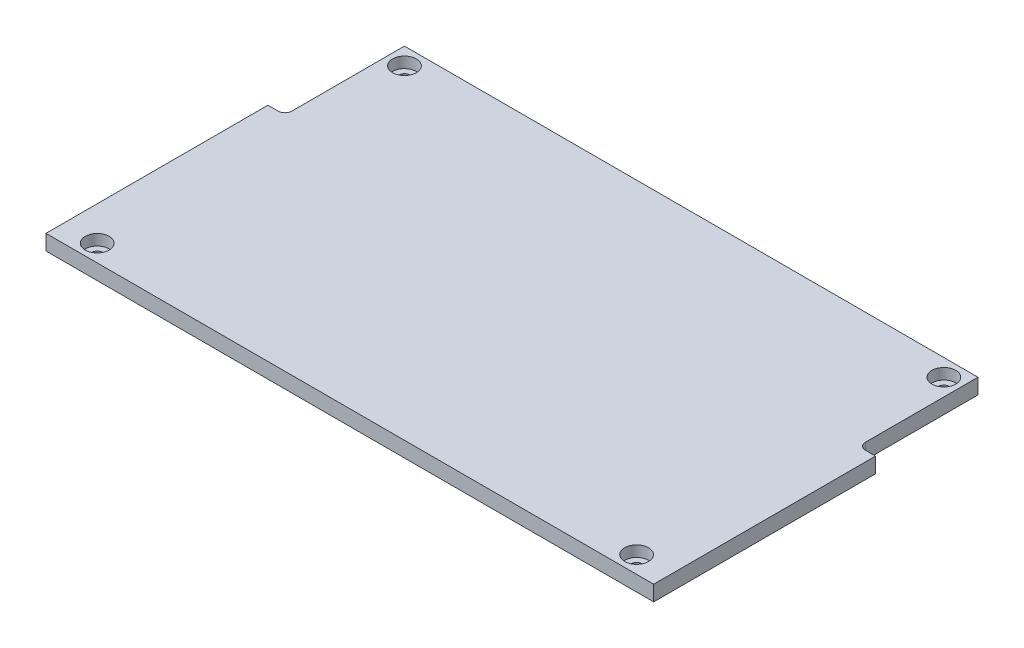
SolidWorks part; units mm, degrees
ref_plane "Ebene vorne" through (0, 0, 0) normal (0, 0, 1) x (1, 0, 0)
ref_plane "Ebene oben" through (0, 0, 0) normal (0, 1, 0) x (1, 0, 0)
ref_plane "Ebene rechts" through (0, 0, 0) normal (1, 0, 0) x (0, 0, -1)
sketch "Skizze1" plane through (0, 0, 0) normal (0, 1, 0) x (1, 0, 0)
  line L1 (0, 0) -> (-89, 0)
  line L2 (0, 0) -> (0, 50)
  line L3 (0, 50) -> (-89, 50)
  line L4 (-89, 0) -> (-89, 50)
  dimension "D1" = 89
  dimension "D2" = 50
extrude "Aufsatz-Linear austragen1" add sketch "Skizze1" along normal blind 4.5
sketch "Skizze3" plane through (0, 4.5, 0) normal (0, 1, 0) x (1, 0, 0)
  line L1 (0, 0) -> (0, 50) construction
  line L2 (-19, 3) -> (-3, 3)
  line L3 (-19, 3) -> (-19, 15)
  line L4 (-19, 15) -> (-3, 15)
  line L5 (-3, 3) -> (-3, 15)
  line L6 (-19, 3) -> (-3, 15) construction
  line L7 (-19, 15) -> (-3, 3) construction
  line L8 (-89, 0) -> (0, 0) construction
  point P0 (-11, 9)
  dimension "D1" = 3
  dimension "D3" = 12
  dimension "D2" = 3
  dimension "D4" = 16
extrude "Schnitt-Linear austragen2" cut sketch "Skizze3" against normal through all
fillet "Verrundung1" radius 2 4 edges at (-19, 2.25, -3) (-3, 2.25, -3) (-3, 2.25, -15) (-19, 2.25, -15)
pattern_linear "Lineares Muster1" count 3 spacing 16 along (0, 0, -1) count 4 spacing 20 along (-1, 0, 0) of "Schnitt-Linear austragen2", "Verrundung1"
sketch "Skizze2" plane through (0, 4.5, 0) normal (0, 1, 0) x (1, 0, 0)
  line L0 (0, 0) -> (0, 50) construction
  line L1 (-89, 0) -> (0, 0) construction
  circle A0 centre (-79, 45) radius 5
  dimension "D1" = 10
  dimension "D2" = 79
  dimension "D3" = 45
extrude "Aufsatz-Linear austragen2" add sketch "Skizze2" against normal up to surface (4.5 mm away) up to face at (-11, 0, -25)
hole_wizard "Stirnsenkung für M3 Flachkopfschraube mit Schlitz1" positions "Skizze4" profile "Skizze5" counterbore size "M3" standard "DIN" end condition through all
sketch "Skizze4" plane through (0, 4.5, 0) normal (0, 1, 0) x (1, 0, 0)
  line L0 (0, 50) -> (-89, 50) construction
  point P0 (-79, 45)
  dimension "D1" = 10
  dimension "D2" = 5
sketch "Skizze5" plane through (-79, 4.5, -45) normal (1, 0, 0) x (0, 0, 1)
  line L0 (0, 0) -> (0, 4.5)
  line L1 (0, 4.5) -> (1.7, 4.5)
  line L3 (1.7, 4.5) -> (1.7, 3.2)
  line L4 (1.7, 3.2) -> (3.5, 3.2)
  line L5 (3.5, 3.2) -> (3.5, 0)
  line L7 (3.5, 0) -> (0, 0)
  line L11 (0, -6.35) -> (0, 107.95) construction
  dimension "Bohrerdurchmesser" = 3.4
  dimension "Bohrungstiefe" = 4.5
  dimension "Senkdurchmesser2" = 7
  dimension "Senktiefe2" = 3.2
fillet "Verrundung3" radius 3 2 edges at (-79, 2.25, -40) (-74.4174, 2.25, -47)
sketch "Skizze6" plane through (0, 0, 0) normal (0, -1, 0) x (1, 0, 0)
  line L0 (-79, -29) -> (-79, -21) construction
  line L1 (0, 0) -> (-79, 0)
  line L2 (0, 0) -> (0, -47)
  line L3 (0, -47) -> (-71.0627, -47)
  line L4 (-79, 0) -> (-79, -37)
  line L5 (-71.0627, -37) -> (-79, -37)
  line L6 (-71.0627, -37) -> (-71.0627, -47)
  line L11 (-45, -47) -> (-57, -47) construction
  line L12 (-65, -47) -> (-71.0627, -47) construction
extrude "Schnitt-Linear austragen3" cut sketch "Skizze6" against normal blind 1.5
sketch "Skizze7" plane through (0, 1.5, 0) normal (0, -1, 0) x (1, 0, 0)
  line L0 (-79, 0) -> (0, 0)
  line L1 (0, 0) -> (0, -47)
  line L6 (0, -50) -> (0, -47)
  line L7 (0, -47) -> (-71.0627, -47)
  line L8 (-79, -37.5838) -> (-79, 0)
  line L9 (-79, 0) -> (-89, 0)
  line L10 (-89, 0) -> (-89, -50)
  line L11 (-89, -50) -> (0, -50)
  line L13 (0, -47) -> (-71.0627, -47)
  line L14 (-79, -37.5838) -> (-79, 0)
  arc A3 (-74.0392, -44.375) -> (-71.0627, -47) centre (-71.0627, -44) ccw
  arc A4 (-74.0392, -44.375) -> (-77.125, -40.3649) centre (-79, -45) ccw
  arc A5 (-79, -37.5838) -> (-77.125, -40.3649) centre (-76, -37.5838) ccw
  arc A6 (-74.0392, -44.375) -> (-71.0627, -47) centre (-71.0627, -44) ccw
  arc A7 (-74.0392, -44.375) -> (-77.125, -40.3649) centre (-79, -45) ccw
  arc A8 (-79, -37.5838) -> (-77.125, -40.3649) centre (-76, -37.5838) ccw
  dimension "D1" = 0
extrude "Aufsatz-Linear austragen3" add sketch "Skizze7" against normal up to surface (3 mm away) up to face at (-79, 4.5, -41.5)
mirror "Spiegeln1" about plane through (0, 4.5, 0) normal (0, 0, -1) of bodies 124 115
sketch "Skizze8" plane through (0, 0, 0) normal (0, -1, 0) x (1, 0, 0)
  line L5 (0, -50) -> (-89, -50) construction
  line L7 (-89, -50) -> (-89, 50) construction
  line L9 (-94, -50) -> (-84, -50)
  line L10 (-94, -50) -> (-94, -15)
  line L11 (-94, -15) -> (-84, -15)
  line L12 (-84, -50) -> (-84, -15)
  line L13 (-94, -50) -> (-84, -15) construction
  line L14 (-94, -15) -> (-84, -50) construction
  point P9 (-89, -32.5)
  dimension "D1" = 35
  dimension "D4" = 5
extrude "Schnitt-Linear austragen4" cut sketch "Skizze8" against normal through all
fillet "Verrundung4" radius 2 1 edges at (-84, 2.25, -15)
mirror "Spiegeln2" about plane through (0, 4.5, 0) normal (-1, 0, 0) of bodies 125 116
